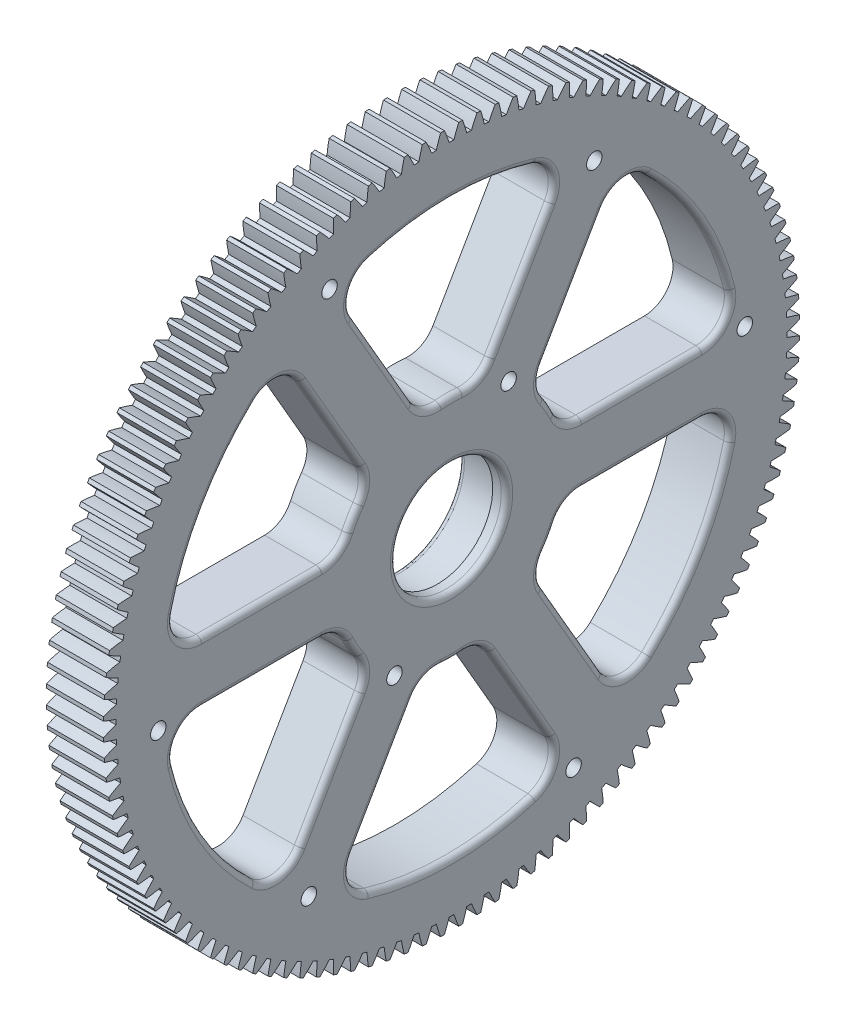
SolidWorks part; units mm, degrees
ref_plane "Plane1" through (0, 0, 0) normal (0, 0, 1) x (1, 0, 0)
ref_plane "Plane2" through (0, 0, 0) normal (0, 1, 0) x (1, 0, 0)
ref_plane "Plane3" through (0, 0, 0) normal (1, 0, 0) x (0, 0, -1)
other "Configuration Table"
sketch "HoldingSke" plane through (0, 0, 0) normal (0, 1, 0) x (1, 0, 0)
  line L0 (0, 0) -> (-254, -439.9409)
  line L1 (-15, 0) -> (100, 0) construction
  line L2 (0, 0) -> (-2.1039, 2.3779)
  line L3 (0, 0) -> (-11.863, 4.5341)
  line L4 (0, 0) -> (-4.318, 7.479)
  line L5 (0, 0) -> (-47.5972, -17.7524)
  line L6 (0, 0) -> (-10.5278, -7.1032)
  line L7 (-2.1039, 2.3779) -> (8.8308, 51.9871)
  line L8 (-76.2, 54.61) -> (-44.6786, 54.61)
  line L9 (-71.009, 38.7566) -> (-53.1078, 45.2721)
  line L10 (-76.2, 71.12) -> (104.1128, 71.12)
  line L11 (0, 0) -> (-12.7, 0)
  line L12 (-76.2, 101.6) -> (-76.1492, 101.6)
  line L13 (24.9733, 27.94) -> (52.9518, 28.4284)
  line L14 (24.9733, 27.94) -> (25.0241, 27.9398)
  line L15 (24.9733, 27.94) -> (100.4021, 29.52)
  circle A0 centre (0, 0) radius 14.2875
  circle A1 centre (0, 0) radius 38.1
  circle A2 centre (0, 0) radius 38.1
  circle A3 centre (0, 0) radius 14.2875
  dimension "Num_teeth" = 120
  dimension "H" = 19.05
  dimension "Pitch_radius" = 180.3128
  dimension "Width" = 12.7
  dimension "Thickness" = 12.7
sketch "BasProSke" plane through (0, 0, 0) normal (0, 1, 0) x (1, 0, 0)
  line L0 (-10, 0) -> (60, 0) construction
  line L1 (0, 0) -> (0, 77.47)
  line L2 (0, 0) -> (12.7, 0)
  line L3 (12.7, 0) -> (12.7, 77.47)
  line L4 (12.7, 77.47) -> (0, 77.47)
  dimension "Thickness" = 12.7
  dimension "Diameter" = 154.94
revolve "Base-Revolve" add sketch "BasProSke" angle 360 about L0
sketch "TooCutSke" plane through (0, 0, 0) normal (1, 0, 0) x (0, 0, -1)
  line L1 (0, 0) -> (0, 107) construction
  line L2 (0, 0) -> (-1.0863, 76.1923) construction
  line L3 (0, 0) -> (-3.9891, 152.3369) construction
  line L4 (-1.0863, 76.1923) -> (-1.9945, 76.1685) construction
  arc A0 (0.5305, 74.6233) -> (-0.5305, 74.6233) centre (0, 0) ccw
  arc A1 (1.616, 77.4785) -> (-1.616, 77.4785) centre (0, 0) ccw
  circle A2 centre (0, 0) radius 76.2 construction
  circle A3 centre (0, 0) radius 71.6046 construction
  arc A4 (-0.5305, 74.6233) -> (-1.616, 77.4785) centre (-29.5279, 65.2328) ccw
  arc A5 (1.616, 77.4785) -> (0.5305, 74.6233) centre (29.5279, 65.2328) ccw
extrude "ToothCut" cut sketch "TooCutSke" along normal through all
fillet "Breaks" [suppressed] radius 0.0254 tangent propagation no
fillet "RootFillets" [suppressed] radius 0.3048
pattern_circular "TeethCuts" count 120 every 3 about axis through (-10, 0, 0) along (1, 0, 0) of "ToothCut", "RootFillets", "Breaks"
sketch "HubNeaOneSke" plane through (0, 0, 0) normal (-1, 0, 0) x (0, 0, 1)
  circle A0 centre (0, 0) radius 38.1
  dimension "Diameter" = 76.2
extrude "HubNearOne" [suppressed] add sketch "HubNeaOneSke" along normal blind 38.1001
sketch "HubNeaBotSke" plane through (0, 0, 0) normal (-1, 0, 0) x (0, 0, 1)
  circle A0 centre (0, 0) radius 38.1
  dimension "Diameter" = 76.2
extrude "HubNearBoth" [suppressed] add sketch "HubNeaBotSke" along normal blind 19.05
ref_plane "FarPln" through (12.7, 0, 0) normal (1, 0, 0) x (0, 0, -1)
sketch "HubFarSke" plane through (12.7, 0, 0) normal (1, 0, 0) x (0, 0, -1)
  circle A0 centre (0, 0) radius 38.1
  dimension "Diameter" = 76.2
extrude "HubFar" [suppressed] add sketch "HubFarSke" along normal blind 19.05
sketch "BorSke" plane through (0, 0, 0) normal (1, 0, 0) x (0, 0, -1)
  circle A0 centre (0, 0) radius 14.2875
  dimension "Diameter" = 28.575
extrude "Bore" cut sketch "BorSke" along normal mid plane 101.6001
sketch "KeySke" plane through (0, 0, 0) normal (1, 0, 0) x (0, 0, -1)
  line L0 (-3.175, 0) -> (-3.175, 17.2339)
  line L1 (-3.175, 17.2339) -> (3.175, 17.2339)
  line L2 (3.175, 17.2339) -> (3.175, 0)
  line L3 (0, 0) -> (0, 34) construction
  line L4 (-3.175, 0) -> (3.175, 0)
  dimension "Width" = 6.35
extrude "Keyway" [suppressed] cut sketch "KeySke" along normal mid plane 101.6001
pattern_circular "Keyway2" [suppressed] count 2 every 90 about axis through (-10, 0, 0) along (1, 0, 0) reverse direction yes
sketch "Sketch2" plane through (12.7, 0, 0) normal (1, 0, 0) x (0, 0, -1)
  line L13 (8.5632, 28.4268) -> (21.9218, 51.5646)
  line L16 (-21.9218, 51.5646) -> (-8.5632, 28.4268)
  line L17 (0, 0) -> (0, 86.3173) construction
  arc A0 (2.4511, 25.2815) -> (-2.4511, 25.2815) centre (0, 0) ccw
  arc A1 (18.2473, 60.8218) -> (-18.2473, 60.8218) centre (0, 0) ccw
  arc A2 (21.9218, 51.5646) -> (18.2473, 60.8218) centre (16.4225, 54.7396) ccw
  arc A3 (2.4511, 25.2815) -> (8.5632, 28.4268) centre (3.0639, 31.6018) ccw
  arc A4 (-2.4511, 25.2815) -> (-8.5632, 28.4268) centre (-3.0639, 31.6018) cw
  arc A5 (-18.2473, 60.8218) -> (-21.9218, 51.5646) centre (-16.4225, 54.7396) ccw
  point P3 (0, 63.5)
  point P7 (0, 25.4)
  point P13 (6.35, 24.5934)
  point P16 (-6.35, 24.5934)
  dimension "D1" = 50.8
  dimension "D2" = 127
  dimension "D5" = 6.35
  dimension "D3" = 60
  dimension "D4" = 12.7
extrude "Cut-Extrude1" cut sketch "Sketch2" against normal up to surface (12.7 mm away) up to face at (0, 0, -14.2875)
pattern_circular "CirPattern1" count 6 over 360 about axis through (12.7, 0, 0) along (1, 0, 0) of "Cut-Extrude1"
sketch "Sketch3" plane through (12.7, 0, 0) normal (1, 0, 0) x (0, 0, -1)
  circle A0 centre (0, 0) radius 14.2875 construction
  circle A1 centre (0, 0) radius 14.2875
  circle A2 centre (0, 0) radius 12.3434 construction
  circle A3 centre (0, 0) radius 12.3434
extrude "Boss-Extrude2" add sketch "Sketch3" against normal up to surface (3.175 mm away)
fillet "Fillet1" radius 1.27 50 edges at (12.7, -18.1476, 19.4934) (12.7, -33.1982, 27.016) (12.7, -47.8748, 38.2725) (12.7, -31.75, 54.9926) (12.7, -9.2075, 60.597) (12.7, -6.7975, 42.2585) (12.7, -7.808, 25.463) (12.7, -57.0823, -22.3246) (12.7, -63.5, 0) (12.7, -57.0823, 22.3246) (12.7, -39.9957, 15.2425) (12.7, -25.9556, 5.9696) (12.7, -25.4, 0) (12.7, -25.9556, -5.9696) (12.7, -9.2075, -60.597) (12.7, -31.75, -54.9926) (12.7, -47.8748, -38.2725) (12.7, -33.1982, -27.016) (12.7, -18.1476, -19.4934) (12.7, -12.7, -21.997) (12.7, -7.808, -25.463) (12.7, 9.2075, -60.597) (12.7, 6.7975, -42.2585) (12.7, 7.808, -25.463) (12.7, 12.7, -21.997) (12.7, 18.1476, -19.4934) (12.7, 33.1982, -27.016) (12.7, 47.8748, -38.2725) (12.7, 18.1476, 19.4934) (12.7, 12.7, 21.997) (12.7, 7.808, 25.463) (12.7, 6.7975, 42.2585) (12.7, 9.2075, 60.597) (12.7, 31.75, 54.9926) (12.7, 47.8748, 38.2725) (12.7, 57.0823, -22.3246) (12.7, 39.9957, -15.2425) (12.7, 25.9556, -5.9696) (12.7, 25.4, 0) (12.7, 25.9556, 5.9696) (12.7, 39.9957, 15.2425) (12.7, 57.0823, 22.3246) (12.7, -12.7, 21.997) (12.7, -39.9957, -15.2425) (12.7, -6.7975, -42.2585) (12.7, 31.75, -54.9926) (12.7, 33.1982, 27.016) (12.7, 63.5, 0) (0, 0, -14.2875) (12.7, 0, -12.3434)
hole_wizard "#8-32 Tapped Hole1" positions "Sketch4" profile "Sketch5" tap size "#8-32" standard "ANSI Inch"
sketch "Sketch4" plane through (12.7, 0, 0) normal (1, 0, 0) x (0, 0, -1)
  point P0 (-27.1438, 59.6656)
  point P3 (12.7, 21.997)
  point P6 (31.75, 54.9926)
  point P9 (65.2438, 6.3256)
  point P12 (-12.7, -21.997)
  point P15 (-31.75, -54.9926)
  point P18 (-65.2438, -6.3256)
  point P21 (27.1438, -59.6656)
sketch "Sketch5" plane through (12.7, 59.6656, 27.1438) normal (0, 1, 0) x (0, 0, -1)
  line L0 (0, 0) -> (0, 13.7378)
  line L1 (0, 13.7378) -> (1.7272, 12.7)
  line L2 (1.7272, 12.7) -> (1.7272, 0)
  line L5 (1.7272, 0) -> (0, 0)
  line L10 (0, 13.7378) -> (-1.7272, 12.7) construction
  line L11 (0, -6.35) -> (0, 107.95) construction
  dimension "Tap Drill Dia." = 3.4544
  dimension "Tap Drill Depth" = 12.7
  dimension "Drill Angle" = 118
cosmetic thread "Hole Thread1" parameters "D1"=8.382, "D2"=4.1656
cosmetic thread "Hole Thread2" parameters "D1"=8.382, "D2"=4.1656
cosmetic thread "Hole Thread3" parameters "D1"=8.382, "D2"=4.1656
cosmetic thread "Hole Thread4" parameters "D1"=8.382, "D2"=4.1656
cosmetic thread "Hole Thread5" parameters "D1"=8.382, "D2"=4.1656
cosmetic thread "Hole Thread6" parameters "D1"=8.382, "D2"=4.1656
cosmetic thread "Hole Thread7" parameters "D1"=8.382, "D2"=4.1656
cosmetic thread "Hole Thread8" parameters "D1"=8.382, "D2"=4.1656
equation "' \"Pitch@HoldingSke\" = 4"
equation "' \"Num_teeth@HoldingSke\" = 12"
equation "' \"Ap@HoldingSke\" =  20"
equation "' \"Ap@HoldingSke\" = 20"
equation "' \"Width@HoldingSke\" = 0.5"
equation "' \"Hub_dia@HoldingSke\"= 1"
equation "' \"Hub_dia@HoldingSke\" = 1"
equation "' \"Overall_len@HoldingSke\" = 1.0"
equation "' \"Bore@HoldingSke\" = 0.75"
equation "' \"T_dim@HoldingSke\" = 0.85"
equation "' \"Width@KeySke\" = 0.25"
equation "' \"Show_teeth@HoldingSke\" = 13"
equation "' \"Backlash@HoldingSke\" = 0.009"
equation "' \"Addendum_fac@HoldingSke\" = 1.0"
equation "' \"Dedendum_fac@HoldingSke\" = 1.25"
equation "' \"Dedendum_add@HoldingSke\" = 0.00005"
equation "' \"Clearance_fac@HoldingSke\" = 0.25"
equation "' \"Pitch@HoldingSke\" = 0.5"
equation "' \"Num_teeth@HoldingSke\" = 23"
equation "' \"Show_teeth@HoldingSke\" = 23"
equation "' \"Backlash@HoldingSke\" = 0.0375"
equation "\"Overcut_dia@TooCutSke\" = (\"Num_teeth@HoldingSke\" + 2 * \"Addendum_fac@HoldingSke\") / \"Pitch@HoldingSke\" + 0.002"
equation "\"Pitch_dia@TooCutSke\" = \"Num_teeth@HoldingSke\" / \"Pitch@HoldingSke\""
equation "\"Base_dia@TooCutSke\" = \"Num_teeth@HoldingSke\" / \"Pitch@HoldingSke\" * cos((\"Ap@HoldingSke\"  * 3.14159265 / 180))"
equation "\"Root_dia@TooCutSke\" = (\"Num_teeth@HoldingSke\" + 2) / \"Pitch@HoldingSke\" - 2 * (\"Addendum_fac@HoldingSke\" + \"Dedendum_fac@HoldingSke\") / \"Pitch@HoldingSke\" - \"Dedendum_add@HoldingSke\" * 2"
equation "\"Half_ang@TooCutSke\" = 180 / \"Num_teeth@HoldingSke\""
equation "\"Half_CT@TooCutSke\" = \"Num_teeth@HoldingSke\" / \"Pitch@HoldingSke\" * sin((3.14159265 / 2 / \"Num_teeth@HoldingSke\")) / 2 - 7 * \"Backlash@HoldingSke\" / 4"
equation "\"Flank_rad@TooCutSke\" = \"Num_teeth@HoldingSke\" / \"Pitch@HoldingSke\" / 5"
equation "\"Radius@RootFillets\" = \"Clearance_fac@HoldingSke\" / \"Pitch@HoldingSke\" + \"Dedendum_add@HoldingSke\""
equation "\"Break_rad@Breaks\" = 0.02 / \"Pitch@HoldingSke\""
equation "\"Thickness@HoldingSke\" = \"Width@HoldingSke\""
equation "\"OAL@HoldingSke\" = \"Thickness@HoldingSke\""
equation "\"MHD@HoldingSke\" = (\"Num_teeth@HoldingSke\" + 2) / \"Pitch@HoldingSke\" - 2 * (\"Addendum_fac@HoldingSke\" + \"Dedendum_fac@HoldingSke\")  / \"Pitch@HoldingSke\" - \"Dedendum_add@HoldingSke\" * 2"
equation "\"MBD@HoldingSke\" = (\"Num_teeth@HoldingSke\" + 2) / \"Pitch@HoldingSke\" - 2 * (\"Addendum_fac@HoldingSke\" + \"Dedendum_fac@HoldingSke\")  / \"Pitch@HoldingSke\" - \"Dedendum_add@HoldingSke\" * 2 - 0.002"
equation "\"MHD@HoldingSke\" = ((sgn( \"MHD@HoldingSke\" - \"Hub_dia@HoldingSke\" )-1)*( \"MHD@HoldingSke\" - \"Hub_dia@HoldingSke\" ))/-2+ \"Hub_dia@HoldingSke\""
equation "\"MBD@HoldingSke\" = ((sgn( \"MBD@HoldingSke\" - \"Bore@HoldingSke\" )-1)*( \"MBD@HoldingSke\" - \"Bore@HoldingSke\" ))/-2+ \"Bore@HoldingSke\""
equation "\"OAL@HoldingSke\" = ((sgn( \"OAL@HoldingSke\" - \"Overall_len@HoldingSke\" )+1)*( \"OAL@HoldingSke\" - \"Overall_len@HoldingSke\" ))/2 + \"Overall_len@HoldingSke\" + 0.000002"
equation "\"Num_teeth@TeethCuts\" = int( \"Show_teeth@HoldingSke\" ) + 1"
equation "\"Num_teeth@TeethCuts\" = ((sgn( \"Num_teeth@TeethCuts\" - \"Num_teeth@HoldingSke\" )-1)*( \"Num_teeth@TeethCuts\" - \"Num_teeth@HoldingSke\" ))/-2+ \"Num_teeth@HoldingSke\""
equation "\"Num_teeth@TeethCuts\" = ((sgn( \"Num_teeth@TeethCuts\" - 2.0)+1)*( \"Num_teeth@TeethCuts\" - 2.0))/2 +2.0"
equation "\"Angle@TeethCuts\" = 360.0 / \"Num_teeth@HoldingSke\""
equation "\"Diameter@BasProSke\" = (\"Num_teeth@HoldingSke\" + 2 * \"Addendum_fac@HoldingSke\") / \"Pitch@HoldingSke\""
equation "\"Thickness@BasProSke\"  = \"Thickness@HoldingSke\""
equation "' \"Fillet_rad@BasProSke\" =  \"Thickness@HoldingSke\" * 0.05"
equation "' \"Fillet_rad@BasProSke\" = \"Thickness@HoldingSke\" * 0.05"
equation "\"MHD@HoldingSke\" = ((sgn( \"MHD@HoldingSke\" - \"Root_dia@TooCutSke\" )-1)*( \"MHD@HoldingSke\" - \"Root_dia@TooCutSke\" ))/-2+ \"Root_dia@TooCutSke\""
equation "\"Diameter@HubNeaOneSke\" = \"MHD@HoldingSke\""
equation "\"Length@HubNearOne\" = \"OAL@HoldingSke\" - \"Thickness@BasProSke\""
equation "\"Diameter@HubNeaBotSke\" = \"MHD@HoldingSke\""
equation "\"Length@HubNearBoth\" = ( \"OAL@HoldingSke\" - \"Thickness@BasProSke\" ) / 2.0"
equation "\"Thickness@FarPln\" = \"Thickness@BasProSke\""
equation "\"Diameter@HubFarSke\" = \"MHD@HoldingSke\""
equation "\"Length@HubFar\" = ( \"OAL@HoldingSke\" - \"Thickness@BasProSke\" ) / 2.0"
equation "\"Diameter@BorSke\" = \"MBD@HoldingSke\""
equation "\"D1@Bore\" = \"OAL@HoldingSke\" * 2.0"
equation "\"D1@Keyway\" = \"OAL@HoldingSke\" * 2.0"
equation "\"Offset@KeySke\" = \"T_dim@HoldingSke\" - \"MBD@HoldingSke\" / 2.0"
